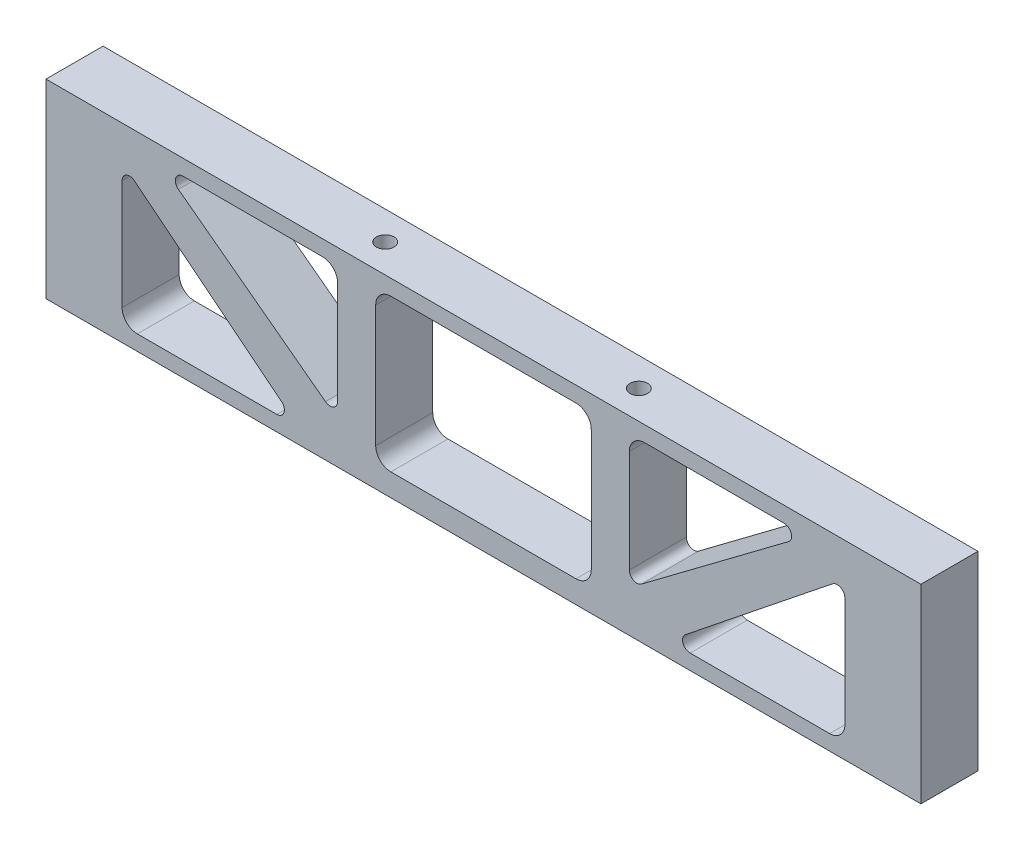
SolidWorks part; units mm, degrees
material "PE High Density"
ref_plane "Front Plane" through (0, 0, 0) normal (0, 0, 1) x (1, 0, 0)
ref_plane "Top Plane" through (0, 0, 0) normal (0, 1, 0) x (1, 0, 0)
ref_plane "Right Plane" through (0, 0, 0) normal (1, 0, 0) x (0, 0, -1)
sketch "Sketch1" plane through (0, 0, 0) normal (0, 0, 1) x (1, 0, 0)
  line L0 (-24.3417, 15.875) -> (-24.3417, -15.875) construction
  line L1 (-73.025, 15.875) -> (73.025, 15.875)
  line L2 (-73.025, 15.875) -> (-73.025, -15.875)
  line L3 (-73.025, -15.875) -> (73.025, -15.875)
  line L4 (73.025, 15.875) -> (73.025, -15.875)
  line L5 (-73.025, 15.875) -> (73.025, -15.875) construction
  line L6 (-73.025, -15.875) -> (73.025, 15.875) construction
  line L7 (24.3417, 15.875) -> (24.3417, -15.875) construction
  line L9 (-69.85, -12.7) -> (-27.5167, 12.7) construction
  line L10 (-69.85, -12.7) -> (-69.85, 12.7) construction
  line L11 (-64.3071, -11.2256) -> (-29.9209, 9.4061)
  line L12 (-73.025, -15.875) -> (-24.3417, -15.875)
  line L13 (-73.025, -15.875) -> (-73.025, 15.875)
  line L14 (-73.025, 15.875) -> (-24.3417, 15.875)
  line L15 (-24.3417, -15.875) -> (-24.3417, 15.875) construction
  line L16 (-69.85, 12.7) -> (-27.5167, 12.7) construction
  line L17 (-27.5167, -12.7) -> (-27.5167, 12.7) construction
  line L18 (-69.85, -12.7) -> (-27.5167, -12.7) construction
  line L19 (-67.4457, -9.4061) -> (-33.0595, 11.2256)
  line L20 (-69.0332, -14.0613) -> (-26.6999, 11.3387) construction
  line L21 (-69.85, -8.0448) -> (-69.85, 11.1125)
  line L22 (-70.6668, -11.3387) -> (-28.3334, 14.0613) construction
  line L23 (-68.2625, 12.7) -> (-33.4679, 12.7)
  line L24 (-63.8988, -12.7) -> (-29.1042, -12.7)
  line L25 (-27.5167, -11.1125) -> (-27.5167, 8.0448)
  line L26 (-15.6238, -11.2256) -> (18.7624, 9.4061)
  line L27 (-18.7624, -9.4061) -> (15.6238, 11.2256)
  line L28 (-21.1667, -8.0448) -> (-21.1667, 11.1125)
  line L29 (-19.5792, 12.7) -> (15.2154, 12.7)
  line L30 (-15.2154, -12.7) -> (19.5792, -12.7)
  line L31 (21.1667, -11.1125) -> (21.1667, 8.0448)
  line L32 (-21.1667, -12.7) -> (21.1667, 12.7) construction
  line L33 (-21.1667, -12.7) -> (-21.1667, 12.7) construction
  line L34 (-21.1667, 12.7) -> (21.1667, 12.7) construction
  line L35 (21.1667, -12.7) -> (21.1667, 12.7) construction
  line L36 (-21.1667, -12.7) -> (21.1667, -12.7) construction
  line L37 (33.0595, -11.2256) -> (67.4457, 9.4061)
  line L38 (29.9209, -9.4061) -> (64.3071, 11.2256)
  line L39 (27.5167, -8.0448) -> (27.5167, 11.1125)
  line L40 (29.1042, 12.7) -> (63.8988, 12.7)
  line L41 (33.4679, -12.7) -> (68.2625, -12.7)
  line L42 (69.85, -11.1125) -> (69.85, 8.0448)
  line L43 (27.5167, -12.7) -> (69.85, 12.7) construction
  line L44 (27.5167, -12.7) -> (27.5167, 12.7) construction
  line L45 (27.5167, 12.7) -> (69.85, 12.7) construction
  line L46 (69.85, -12.7) -> (69.85, 12.7) construction
  line L47 (27.5167, -12.7) -> (69.85, -12.7) construction
  line L59 (-64.3071, -11.2256) -> (-15.6238, -11.2256) construction
  line L60 (-69.85, 15.875) -> (-69.85, -15.875)
  arc A0 (-33.4679, 12.7) -> (-33.0595, 11.2256) centre (-33.4679, 11.9062) cw
  arc A1 (-69.85, -8.0448) -> (-67.4457, -9.4061) centre (-68.2625, -8.0448) ccw
  arc A2 (-69.85, 11.1125) -> (-68.2625, 12.7) centre (-68.2625, 11.1125) cw
  arc A3 (-27.5167, 8.0448) -> (-29.9209, 9.4061) centre (-29.1042, 8.0448) ccw
  arc A4 (-63.8988, -12.7) -> (-64.3071, -11.2256) centre (-63.8988, -11.9062) cw
  arc A5 (-27.5167, -11.1125) -> (-29.1042, -12.7) centre (-29.1042, -11.1125) cw
  arc A6 (15.2154, 12.7) -> (15.6238, 11.2256) centre (15.2154, 11.9062) cw
  arc A7 (-21.1667, -8.0448) -> (-18.7624, -9.4061) centre (-19.5792, -8.0448) ccw
  arc A8 (-21.1667, 11.1125) -> (-19.5792, 12.7) centre (-19.5792, 11.1125) cw
  arc A9 (21.1667, 8.0448) -> (18.7624, 9.4061) centre (19.5792, 8.0448) ccw
  arc A10 (-15.2154, -12.7) -> (-15.6238, -11.2256) centre (-15.2154, -11.9062) cw
  arc A11 (21.1667, -11.1125) -> (19.5792, -12.7) centre (19.5792, -11.1125) cw
  arc A12 (63.8988, 12.7) -> (64.3071, 11.2256) centre (63.8988, 11.9062) cw
  arc A13 (27.5167, -8.0448) -> (29.9209, -9.4061) centre (29.1042, -8.0448) ccw
  arc A14 (27.5167, 11.1125) -> (29.1042, 12.7) centre (29.1042, 11.1125) cw
  arc A15 (69.85, 8.0448) -> (67.4457, 9.4061) centre (68.2625, 8.0448) ccw
  arc A16 (33.4679, -12.7) -> (33.0595, -11.2256) centre (33.4679, -11.9062) cw
  arc A17 (69.85, -11.1125) -> (68.2625, -12.7) centre (68.2625, -11.1125) cw
  point P0 (0, 0)
  point P26 (-30.6022, 12.7)
  point P29 (-69.85, -10.8487)
  point P35 (-27.5167, 10.8487)
  point P38 (-66.7645, -12.7)
  dimension "D7" = 0.7937
  dimension "D8" = 1.5875
  dimension "D9" = 1.5875
  dimension "D10" = 1.5875
  dimension "D11" = 0.7937
  dimension "D12" = 1.5875
  dimension "D1" = 31.75
  dimension "CrossBraceLength" = 146.05
  dimension "D4" = 48.6833
  dimension "D14" = 48.6833
  dimension "D6" = 3.175
  dimension "D2" = 1.5875
  dimension "D5" = 1.5875
  dimension "D3" = 3
  dimension "D13" = 3
extrude "Boss-Extrude1" [suppressed] add sketch "Sketch1" along normal blind 9.525
sketch "Sketch2" plane through (0, 0, 0) normal (0, 0, 1) x (1, 0, 0)
  line L0 (-63.5, 15.3) -> (-63.5, -16.45) construction
  line L1 (-73.025, 15.3) -> (73.025, 15.3)
  line L2 (-73.025, 15.3) -> (-73.025, -16.45)
  line L3 (-73.025, -16.45) -> (73.025, -16.45)
  line L4 (73.025, 15.3) -> (73.025, -16.45)
  line L5 (-73.025, 15.3) -> (73.025, -16.45) construction
  line L6 (-73.025, -16.45) -> (73.025, 15.3) construction
  line L7 (0, 15.3) -> (0, -16.45) construction
  line L8 (-63.5, -16.45) -> (-63.5, 15.3) construction
  line L9 (63.5, 15.3) -> (63.5, -16.45) construction
  line L10 (-21.1667, 15.3) -> (-21.1667, -16.45) construction
  line L11 (-73.025, -0.575) -> (73.025, -0.575) construction
  line L12 (21.1667, 15.3) -> (21.1667, -16.45) construction
  line L14 (-63.5, -16.45) -> (-63.5, 15.3) construction
  line L15 (-63.5, 15.3) -> (-21.1667, 15.3)
  line L19 (-63.5, 15.3) -> (-21.1667, -16.45) construction
  line L20 (-63.5, -16.45) -> (-21.1667, -16.45)
  line L21 (-21.1667, 15.3) -> (-63.5, 15.3)
  line L22 (-63.5, -16.45) -> (-21.1667, -16.45)
  line L23 (-63.5, -16.45) -> (-63.5, 15.3) construction
  line L27 (-63.5, 15.3) -> (-21.1667, -16.45) construction
  line L28 (-50.927, 10.414) -> (-26.3737, -8.001)
  line L29 (-60.325, -11.3725) -> (-60.325, 6.985)
  line L48 (-57.785, -13.9125) -> (-34.5017, -13.9125)
  line L67 (-68.2625, 15.3) -> (-68.2625, -16.45) construction
  line L78 (-58.262, 7.977) -> (-33.7087, -11.6505)
  line L85 (68.2625, 15.875) -> (68.2625, -15.875) construction
  line L96 (73.025, 15.3) -> (73.025, -16.45)
  line L97 (-63.5, 15.3) -> (-24.3417, 15.3)
  line L99 (-60.325, -16.45) -> (-60.325, 15.3) construction
  line L102 (-24.3417, 10.16) -> (-24.3417, -6.985)
  line L104 (-50.165, 12.7) -> (-26.8817, 12.7)
  line L105 (24.3417, 10.16) -> (24.3417, -6.985)
  line L106 (-24.3417, 15.3) -> (-24.3417, -16.45) construction
  line L107 (50.165, 12.7) -> (26.8817, 12.7)
  line L108 (50.927, 10.414) -> (26.3737, -8.001)
  line L109 (57.785, -13.9125) -> (34.5017, -13.9125)
  line L110 (58.262, 7.977) -> (33.7087, -11.6505)
  line L111 (60.325, -11.3725) -> (60.325, 6.985)
  line L112 (0, -16.45) -> (0, -13.275)
  line L114 (-15.4517, 12.7) -> (15.4517, 12.7)
  line L115 (-17.9917, 10.16) -> (-17.9917, -10.16)
  line L116 (-15.4517, -12.7) -> (15.4517, -12.7)
  line L117 (17.9917, 10.16) -> (17.9917, -10.16)
  line L118 (-17.9917, 12.7) -> (17.9917, -12.7) construction
  line L119 (-17.9917, -12.7) -> (17.9917, 12.7) construction
  arc A52 (-57.785, -13.9125) -> (-60.325, -11.3725) centre (-57.785, -11.3725) cw
  arc A53 (-60.325, 6.985) -> (-58.262, 7.977) centre (-59.055, 6.985) cw
  arc A54 (-34.5017, -13.9125) -> (-33.7087, -11.6505) centre (-34.5017, -12.6425) ccw
  arc A55 (-26.8817, 12.7) -> (-24.3417, 10.16) centre (-26.8817, 10.16) cw
  arc A56 (-26.3737, -8.001) -> (-24.3417, -6.985) centre (-25.6117, -6.985) ccw
  arc A57 (-50.927, 10.414) -> (-50.165, 12.7) centre (-50.165, 11.43) cw
  arc A58 (26.3737, -8.001) -> (24.3417, -6.985) centre (25.6117, -6.985) cw
  arc A59 (26.8817, 12.7) -> (24.3417, 10.16) centre (26.8817, 10.16) ccw
  arc A60 (50.927, 10.414) -> (50.165, 12.7) centre (50.165, 11.43) ccw
  arc A61 (57.785, -13.9125) -> (60.325, -11.3725) centre (57.785, -11.3725) ccw
  arc A62 (34.5017, -13.9125) -> (33.7087, -11.6505) centre (34.5017, -12.6425) cw
  arc A63 (60.325, 6.985) -> (58.262, 7.977) centre (59.055, 6.985) ccw
  arc A64 (-15.4517, -12.7) -> (-17.9917, -10.16) centre (-15.4517, -10.16) cw
  arc A65 (-17.9917, 10.16) -> (-15.4517, 12.7) centre (-15.4517, 10.16) cw
  arc A66 (17.9917, 10.16) -> (15.4517, 12.7) centre (15.4517, 10.16) ccw
  arc A67 (17.9917, -10.16) -> (15.4517, -12.7) centre (15.4517, -10.16) cw
  point P18 (-65.405, 13.335)
  point P19 (-23.0717, -18.415)
  point P24 (-63.5, 12.7)
  point P26 (-24.3417, 12.7)
  point P34 (-61.595, 18.415)
  point P36 (-19.2617, -13.335)
  point P65 (0, 0)
  dimension "D8" = 1.27
  dimension "D9" = 1.27
  dimension "D12" = 1.27
  dimension "D13" = 1.27
  dimension "D16" = 2.54
  dimension "D1" = 146.05
  dimension "D2" = 31.75
  dimension "D3" = 9.525
  dimension "D23" = 4.7625
  dimension "D4" = 42.3333
  dimension "D5" = 42.3333
  dimension "D14" = 3.175
  dimension "D15" = 35.9833
  dimension "D7" = 3.175
  dimension "D10" = 3.175
extrude "Boss-Extrude2" add sketch "Sketch2" along normal blind 9.525 contours L4 L1 L2 L3 region at (-68.2625, 13.8054, 0)
sketch "Sketch3" plane through (-73.025, 0, 0) normal (-1, 0, 0) x (0, 0, 1)
  line L0 (9.525, 15.3) -> (0, 15.3) construction
  line L1 (0, -0.575) -> (9.525, -0.575) construction
  line L3 (4.7625, -16.45) -> (4.7625, 15.3) construction
  line L4 (9.525, -16.45) -> (0, -16.45) construction
  line L5 (0, 15.3) -> (0, -16.45) construction
  line L6 (9.525, 15.3) -> (9.525, -16.45) construction
  circle A0 centre (4.7625, 8) radius 2.2479
  circle A1 centre (4.7625, -9.15) radius 2.2479
  dimension "D2" = 4.4958
  dimension "D1" = 7.3
extrude "Cut-Extrude1" [suppressed] cut sketch "Sketch3" against normal blind 11.1125
sketch "Sketch4" plane through (0, 15.3, 0) normal (0, 1, 0) x (1, 0, 0)
  line L2 (17.9917, -9.525) -> (17.9917, 0) construction
  line L3 (17.9917, -9.525) -> (17.9917, 0) construction
  line L4 (73.025, 0) -> (-73.025, 0)
  line L5 (-73.025, 0) -> (-73.025, -9.525)
  line L6 (-73.025, -9.525) -> (73.025, -9.525)
  line L7 (73.025, -9.525) -> (73.025, 0)
  line L8 (73.025, 0) -> (-73.025, 0) construction
  line L9 (-73.025, 0) -> (-73.025, -9.525) construction
  line L10 (-73.025, -9.525) -> (73.025, -9.525) construction
  line L11 (73.025, -9.525) -> (73.025, 0) construction
  line L12 (-17.9917, -9.525) -> (-17.9917, 0) construction
  line L13 (-17.9917, -9.525) -> (-17.9917, 0) construction
  line L14 (-24.3417, -9.525) -> (-24.3417, 0) construction
  line L15 (-24.3417, -9.525) -> (-24.3417, 0) construction
  line L16 (24.3417, -9.525) -> (24.3417, 0) construction
  line L17 (24.3417, -9.525) -> (24.3417, 0) construction
  line L18 (24.3417, -9.525) -> (17.9917, 0) construction
  line L19 (17.9917, -9.525) -> (24.3417, 0) construction
  circle A0 centre (21.1667, -4.7625) radius 1.4732
  dimension "D2" = 2.9464
  dimension "D1" = 0
extrude "Cut-Extrude2" cut sketch "Sketch4" against normal blind 12.7 contours A0
ref_plane "Plane1" through (0, -0.575, 0) normal (0, 1, 0) x (1, 0, 0)
mirror "Mirror2" about plane through (0, -0.575, 0) normal (0, 1, 0) of "Cut-Extrude2" second plane through (0, 0, 0) second plane normal (1, 0, 0)
mirror "Mirror3" [suppressed] about plane through (0, 0, 0) normal (1, 0, 0)
equation "\"Plate Width\" = 3.5in"
equation "\"Plate Thickness\" = 0.375in"
equation "\"Num holes\" = 4"
equation "\"Plate Height\" = 1.25in"
equation "\"Top Plate Width\" = 4.5in"
equation "\"Plate Clearance Hole Diameter\" = 0.125in"
equation "\"Plate Tap Hole Diameter\" = 0.116in"
equation "\"Bottom Plate Length\" = 6.5in"
equation "\"CrossBraceLength@Sketch1\" = \"Bottom Plate Length\" - 2 * \"Plate Thickness\""
equation "\"D1@Sketch1\"=\"Plate Height\""
equation "\"num_triangle_holes\"= 3"
equation "\"D3@Sketch1\"=\"num_triangle_holes\""
equation "\"D4@Sketch1\"=( \"Bottom Plate Length\" - 2 * \"Plate Thickness\" ) / \"num_triangle_holes\""
equation "\"BorderThickness\"= 0.125"
equation "\"D6@Sketch1\"=\"BorderThickness\""
equation "\"D2@Sketch1\"=\"BorderThickness\"/2"
equation "\"D9@Sketch1\"=\"BorderThickness\"/2"
equation "\"D8@Sketch1\"=\"BorderThickness\"/2"
equation "\"D7@Sketch1\"=\"BorderThickness\"/4"
equation "\"D10@Sketch1\"=\"BorderThickness\"/2"
equation "\"D11@Sketch1\"=\"BorderThickness\"/4"
equation "\"D12@Sketch1\"=\"BorderThickness\"/2"
equation "\"D13@Sketch1\"=\"num_triangle_holes\""
equation "\"D14@Sketch1\"=( \"Bottom Plate Length\" - 2 * \"Plate Thickness\" ) / \"num_triangle_holes\""
equation "\"D1@Boss-Extrude1\"=\"Plate Thickness\""
equation "\"D1@Sketch2\"=\"Bottom Plate Length\" - 2 * \"Plate Thickness\""
equation "\"D2@Sketch2\"=\"Plate Height\""
equation "\"wall_thickness\"= 0.375"
equation "\"D3@Sketch2\"=\"wall_thickness\""
equation "\"D1@Boss-Extrude2\"=\"Plate Thickness\""
equation "\"D23@Sketch2\"=\"wall_thickness\"/2"
equation "\"Number Eight Clearance Size\" = 0.177in"
equation "\"D2@Sketch3\"=\"Number Eight Clearance Size\""
equation "\"D1@Cut-Extrude1\"=(0.75 - \"Plate Thickness\") + 0.0625"
equation "\"D4@Sketch2\"=( ( \"Bottom Plate Length\" - 2 * \"Plate Thickness\" ) - \"Plate Thickness\" * 2 ) /3"
equation "\"D5@Sketch2\"=( ( \"Bottom Plate Length\" - 2 * \"Plate Thickness\" ) - \"Plate Thickness\" * 2 ) /3"
equation "\"D14@Sketch2\"=\"BorderThickness\""
equation "\"D15@Sketch2\"=( ( ( \"Bottom Plate Length\" - 2 * \"Plate Thickness\" ) - \"Plate Thickness\" * 2 ) /3 ) - \"BorderThickness\"*2"
